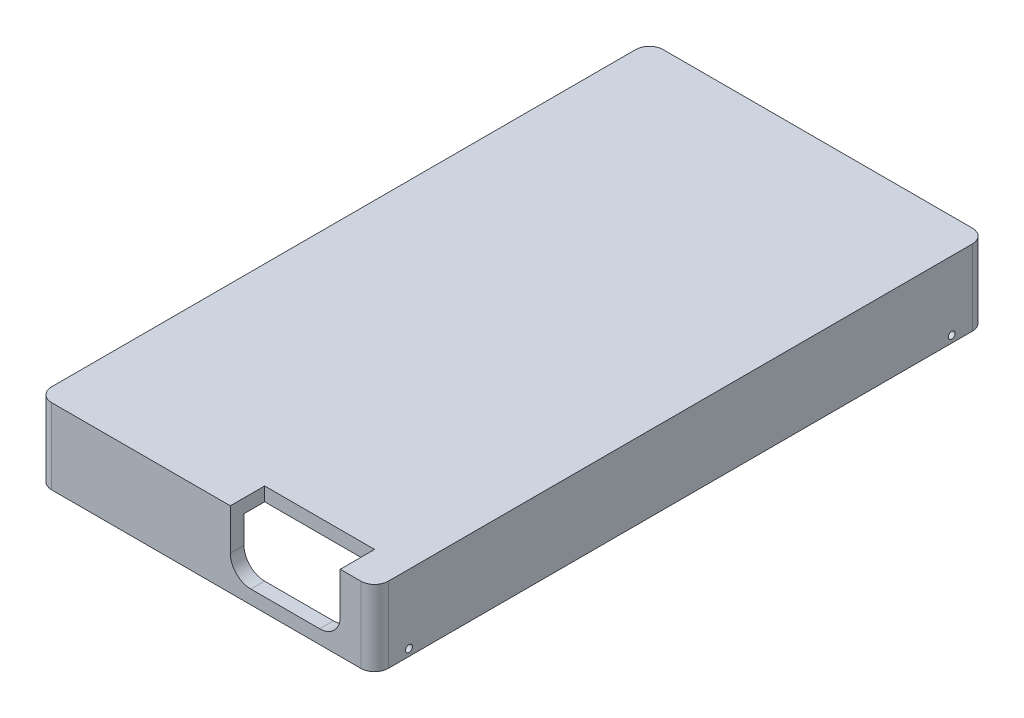
SolidWorks part; units mm, degrees
ref_plane "Front Plane" through (0, 0, 0) normal (0, 0, 1) x (1, 0, 0)
ref_plane "Top Plane" through (0, 0, 0) normal (0, 1, 0) x (1, 0, 0)
ref_plane "Right Plane" through (0, 0, 0) normal (1, 0, 0) x (0, 0, -1)
sketch "Sketch1" plane through (0, 0, 0) normal (0, 1, 0) x (1, 0, 0)
  line L1 (0, 0) -> (57.15, 0)
  line L2 (0, 0) -> (0, 107.95)
  line L3 (0, 107.95) -> (57.15, 107.95)
  line L4 (57.15, 0) -> (57.15, 107.95)
  dimension "D1" = 107.95
  dimension "D2" = 57.15
extrude "Boss-Extrude1" add sketch "Sketch1" along normal blind 2.54
sketch "Sketch2" plane through (0, 2.54, 0) normal (0, 1, 0) x (1, 0, 0)
  line L0 (0, 53.975) -> (57.15, 53.975) construction
  line L1 (0, 107.95) -> (0, 0) construction
  line L2 (57.15, 0) -> (57.15, 107.95) construction
  line L3 (28.575, 107.95) -> (28.575, 0) construction
  line L4 (57.15, 107.95) -> (0, 107.95) construction
  line L5 (0, 0) -> (57.15, 0) construction
  line L7 (-2.54, -2.54) -> (59.69, -2.54)
  line L8 (-2.54, -2.54) -> (-2.54, 110.49)
  line L9 (-2.54, 110.49) -> (59.69, 110.49)
  line L10 (59.69, -2.54) -> (59.69, 110.49)
  line L11 (-2.54, -2.54) -> (59.69, 110.49) construction
  line L12 (-2.54, 110.49) -> (59.69, -2.54) construction
  line L13 (0, 0) -> (57.15, 0)
  line L14 (0, 0) -> (0, 107.95)
  line L15 (0, 107.95) -> (57.15, 107.95)
  line L16 (57.15, 0) -> (57.15, 107.95)
  line L17 (0, 0) -> (57.15, 107.95) construction
  line L18 (0, 107.95) -> (57.15, 0) construction
  point P12 (28.575, 53.975)
  point P17 (28.575, 53.975)
  dimension "D1" = 2.54
  dimension "D2" = 2.54
extrude "Boss-Extrude3" add sketch "Sketch2" against normal blind 13.97
sketch "Sketch3" plane through (0, 0, 2.54) normal (0, 0, 1) x (1, 0, 0)
  line L0 (-2.54, -5.08) -> (59.69, -5.08) construction
  line L1 (-2.54, -11.43) -> (-2.54, 2.54) construction
  line L2 (59.69, -11.43) -> (59.69, 2.54) construction
  line L3 (28.575, 2.54) -> (28.575, -11.43) construction
  line L4 (-2.54, 2.54) -> (59.69, 2.54) construction
  line L5 (-2.54, -11.43) -> (59.69, -11.43) construction
  line L6 (36.83, -5.08) -> (49.53, -5.08) construction
  line L8 (36.83, -8.89) -> (49.53, -8.89)
  line L9 (33.02, -5.08) -> (33.02, 2.54)
  line L10 (53.34, -5.08) -> (53.34, 2.54)
  line L11 (33.02, 2.54) -> (53.34, 2.54)
  arc A0 (33.02, -5.08) -> (36.83, -8.89) centre (36.83, -5.08) ccw
  arc A1 (49.53, -8.89) -> (53.34, -5.08) centre (49.53, -5.08) ccw
  point P14 (43.18, -5.08)
  point P23 (33.02, 2.54)
  dimension "D5" = 3.81
  dimension "D6" = 3.81
  dimension "D1" = 39.37
  dimension "D2" = 12.7
  dimension "D3" = 11.43
  dimension "D4" = 7.62
extrude "Cut-Extrude1" cut sketch "Sketch3" against normal blind 6.35
fillet "Fillet1" radius 2.54 4 edges at (-2.54, -4.445, -110.49) (59.69, -4.445, -110.49) (59.69, -4.445, 2.54) (-2.54, -4.445, 2.54)
sketch "Sketch4" plane through (-2.54, 0, 0) normal (-1, 0, 0) x (0, 0, 1)
  line L0 (-107.95, -10.16) -> (0, -10.16) construction
  line L1 (-107.95, 2.54) -> (-107.95, -11.43) construction
  line L2 (0, -11.43) -> (0, 2.54) construction
  line L3 (-107.95, -11.43) -> (0, -11.43) construction
  line L4 (-53.975, 2.54) -> (-53.975, -11.43) construction
  line L5 (-107.95, 2.54) -> (0, 2.54) construction
  circle A0 centre (-104.14, -10.16) radius 0.635
  circle A1 centre (-3.81, -10.16) radius 0.635
  dimension "D2" = 1.27
  dimension "D3" = 3.81
  dimension "D1" = 1.27
extrude "Cut-Extrude2" cut sketch "Sketch4" against normal through all
